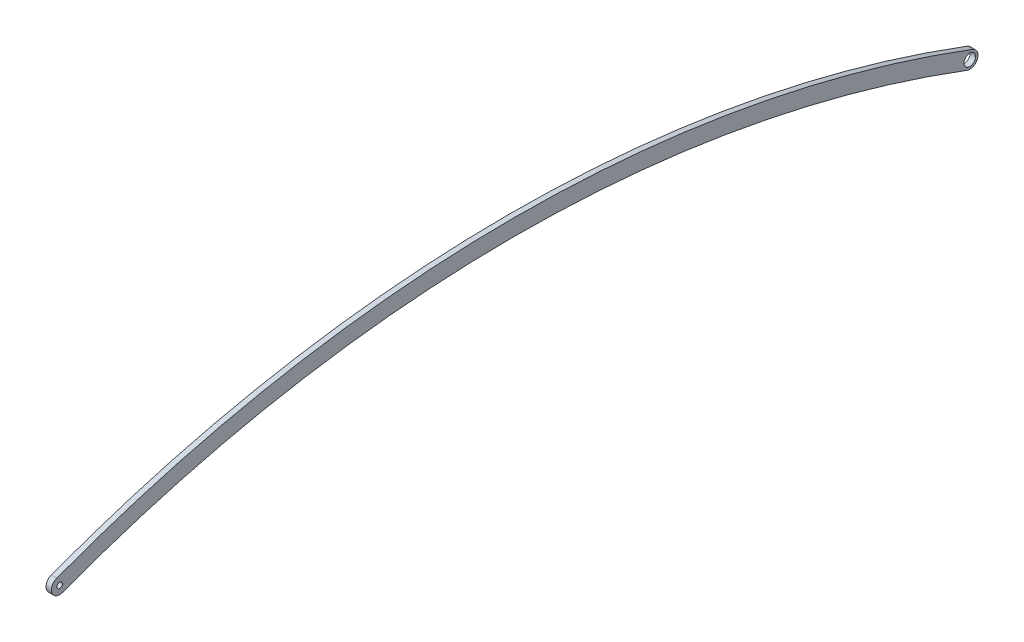
SolidWorks part; units mm, degrees
material "6061-T6 (SS)"
ref_plane "Front Plane" through (0, 0, 0) normal (0, 0, 1) x (1, 0, 0)
ref_plane "Top Plane" through (0, 0, 0) normal (0, 1, 0) x (1, 0, 0)
ref_plane "Right Plane" through (0, 0, 0) normal (1, 0, 0) x (0, 0, -1)
sketch "Sketch1" plane through (0, 0, 0) normal (1, 0, 0) x (0, 0, -1)
  line L0 (0, 0) -> (529.1589, 0) construction
  arc A6 (0, 0) -> (529.1589, 0) centre (264.5794, -701.0337) cw construction
  circle A7 centre (0, 0) radius 1.6
  circle A8 centre (0, 0) radius 4.7625
  circle A11 centre (529.1589, 0) radius 3.3782
  circle A12 centre (529.1589, 0) radius 4.7625
  arc A13 (-1.6816, 4.4557) -> (530.8405, 4.4557) centre (264.5794, -701.0337) cw
  arc A14 (1.6816, -4.4557) -> (527.4772, -4.4557) centre (264.5794, -701.0337) cw
  dimension "D4" = 6.7564
  dimension "D1" = 529.1589
  dimension "D2" = 749.3
  dimension "D3" = 3.2
  dimension "D5" = 9.525
  dimension "D6" = 9.525
extrude "Boss-Extrude1" add sketch "Sketch1" along normal blind 3.175 contours A8 A7 | A8 A14 A12 A13 | A12 A11 region at (0, -2.6319, -3.8065) region at (0, 4.3578, -3.0132) region at (0, 2.6319, -532.9654)
ref_point "Point2"
sketch "Sketch3" plane through (3.175, 0, 0) normal (1, 0, 0) x (0, 0, -1)
  line L0 (518.157, 9.2426) -> (530.8405, 4.4557) construction
  line L1 (529.1589, 0) -> (523.5531, 2.1157) construction
  line L2 (529.1589, 0) -> (527.8472, -6.4085) construction
  line L3 (529.1589, 0) -> (539.6609, -2.1495) construction
  arc A0 (527.4772, -4.4557) -> (530.8405, 4.4557) centre (529.1589, 0) ccw construction
  dimension "D1" = 99.11
